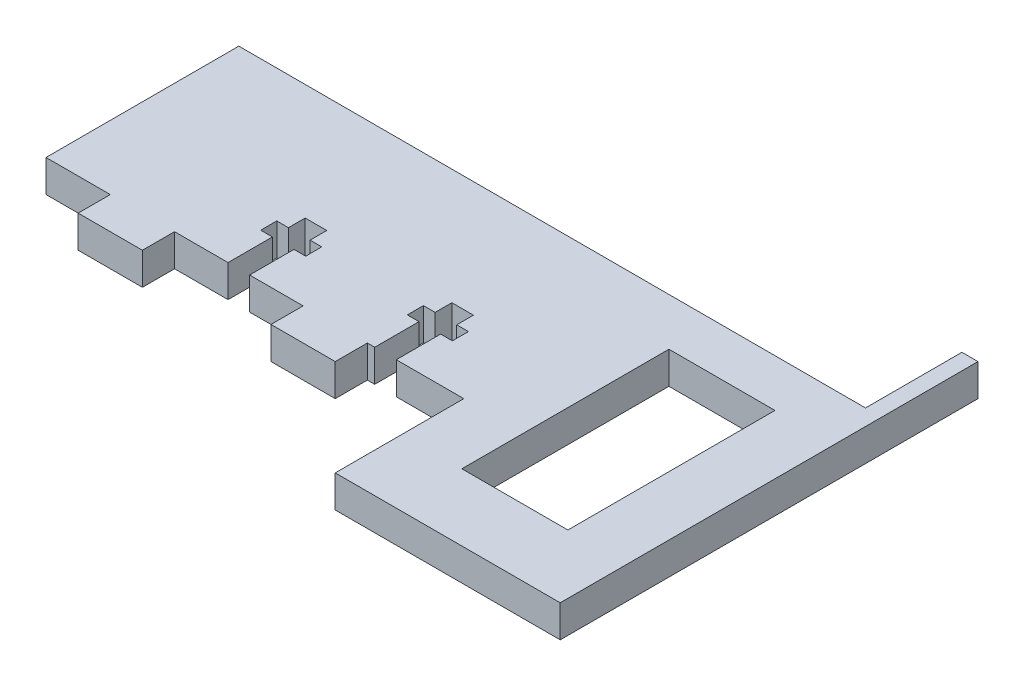
SolidWorks part; units mm, degrees
ref_plane "Front Plane" through (0, 0, 0) normal (0, 0, 1) x (1, 0, 0)
ref_plane "Top Plane" through (0, 0, 0) normal (0, 1, 0) x (1, 0, 0)
ref_plane "Right Plane" through (0, 0, 0) normal (1, 0, 0) x (0, 0, -1)
sketch "Sketch1" plane through (0, 0, 0) normal (0, 1, 0) x (1, 0, 0)
  line L0 (64.8104, 44.2474) -> (64.8104, -38.3026)
  line L1 (-62.1896, 44.2474) -> (64.8104, 44.2474)
  line L2 (-62.1896, 44.2474) -> (-62.1896, -12.9026)
  line L3 (-62.1896, -12.9026) -> (-49.4896, -12.9026)
  line L4 (-36.7896, -12.9026) -> (-11.3896, -12.9026)
  line L6 (1.3104, -12.9026) -> (1.3104, -19.2526)
  line L7 (64.8104, -38.3026) -> (20.3604, -38.3026)
  line L8 (20.3604, -12.9026) -> (20.3604, -38.3026)
  line L9 (1.3104, -19.2526) -> (-11.3896, -19.2526)
  line L10 (-11.3896, -12.9026) -> (-11.3896, -19.2526)
  line L11 (1.3104, -12.9026) -> (20.3604, -12.9026)
  line L12 (-36.7896, -12.9026) -> (-36.7896, -19.2526)
  line L13 (-36.7896, -19.2526) -> (-49.4896, -19.2526)
  line L14 (-49.4896, -12.9026) -> (-49.4896, -19.2526)
  dimension "D1" = 25.4
  dimension "D2" = 57.15
  dimension "D3" = 6.35
  dimension "D4" = 6.35
  dimension "D5" = 12.7
  dimension "D6" = 12.7
  dimension "D7" = 25.4
  dimension "D8" = 19.05
  dimension "D9" = 44.45
  dimension "D10" = 12.7
extrude "Boss-Extrude1" add sketch "Sketch1" along normal blind 6.35
sketch "Sketch2" plane through (0, 0, 0) normal (0, -1, 0) x (1, 0, 0)
  line L0 (20.3604, 12.9026) -> (23.5354, 40.7055)
  line L1 (61.6354, 40.7055) -> (61.6354, -44.2474)
  line L2 (64.8104, -44.2474) -> (-62.1896, -44.2474) construction
  line L3 (61.6354, -44.2474) -> (64.8104, -44.2474)
  line L4 (64.8104, -44.2474) -> (64.8104, 38.3026)
  line L5 (64.8104, 38.3026) -> (64.8104, -44.2474) construction
  line L6 (64.8104, 38.3026) -> (20.3604, 38.3026)
  line L7 (20.3604, 38.3026) -> (20.3604, 12.9026)
  arc A0 (61.6354, 40.7055) -> (23.5354, 40.7055) centre (42.5854, 40.7055) ccw
extrude "Cut-Extrude1" cut sketch "Sketch2" against normal through all rebuild error yes
sketch "Sketch4" plane through (0, 0, 0) normal (0, -1, 0) x (1, 0, 0)
  line L1 (32.1671, 25.0919) -> (53.1176, 25.0919)
  line L2 (32.1671, 25.0919) -> (32.1671, -15.8271)
  line L3 (32.1671, -15.8271) -> (53.1176, -15.8271)
  line L4 (53.1176, 25.0919) -> (53.1176, -15.8271)
extrude "Cut-Extrude2" cut sketch "Sketch4" against normal through all
sketch "Sketch5" plane through (0, 6.35, 0) normal (0, 1, 0) x (1, 0, 0)
  line L0 (-62.1896, 44.2474) -> (-62.1896, -12.9026) construction
  line L1 (61.6354, 44.2474) -> (-62.1896, 44.2474)
  line L2 (61.6354, 44.2474) -> (61.6354, 25.1974)
  line L3 (61.6354, 25.1974) -> (-62.1896, 25.1974)
  line L4 (-62.1896, 44.2474) -> (-62.1896, 25.1974)
  circle A0 centre (47.4162, -54.6607) radius 1.778
  circle A1 centre (37.417, -54.5392) radius 1.778
  circle A2 centre (48.0117, -5.6643) radius 1.778
  circle A3 centre (38.0124, -5.5428) radius 1.778
  dimension "D1" = 19.05
extrude "Cut-Extrude3" cut sketch "Sketch5" against normal through all
sketch "Sketch6" plane through (0, 6.35, 0) normal (0, 1, 0) x (1, 0, 0)
  line L1 (-36.7896, -12.9026) -> (-11.3896, -12.9026) construction
  line L2 (-24.0896, -12.9026) -> (-24.0896, 2.4668) construction
  line B0 (2.759, -12.9026) -> (7.0262, -12.9026)
  line B1 (7.0262, -0.9646) -> (9.3376, -0.9646)
  line B2 (9.3376, -0.9646) -> (9.3376, -4.1396)
  line B3 (9.3376, -4.1396) -> (7.0262, -4.1396)
  line B4 (7.0262, -4.1396) -> (7.0262, -12.9026)
  line B5 (7.0262, -0.9646) -> (7.0262, 2.3374)
  line B6 (7.0262, 2.3374) -> (2.759, 2.3374)
  line B7 (2.759, -0.9646) -> (2.759, 2.3374)
  line B8 (2.759, -4.1396) -> (2.759, -12.9026)
  line B9 (0.4476, -4.1396) -> (2.759, -4.1396)
  line B10 (0.4476, -0.9646) -> (0.4476, -4.1396)
  line B11 (2.759, -0.9646) -> (0.4476, -0.9646)
  line B12 (-26.2232, -12.9026) -> (-21.956, -12.9026)
  line B13 (-21.956, -0.9646) -> (-19.6446, -0.9646)
  line B14 (-19.6446, -0.9646) -> (-19.6446, -4.1396)
  line B15 (-19.6446, -4.1396) -> (-21.956, -4.1396)
  line B16 (-21.956, -4.1396) -> (-21.956, -12.9026)
  line B17 (-21.956, -0.9646) -> (-21.956, 2.3374)
  line B18 (-21.956, 2.3374) -> (-26.2232, 2.3374)
  line B19 (-26.2232, -0.9646) -> (-26.2232, 2.3374)
  line B20 (-26.2232, -4.1396) -> (-26.2232, -12.9026)
  line B21 (-28.5346, -4.1396) -> (-26.2232, -4.1396)
  line B22 (-28.5346, -0.9646) -> (-28.5346, -4.1396)
  line B23 (-26.2232, -0.9646) -> (-28.5346, -0.9646)
sketch_block_instance "TSlot-1"
sketch_block "TSlot" parameters "D1"=3.302, "D2"=3.175
sketch_block_instance "TSlot-3"
extrude "Cut-Extrude4" cut sketch "Sketch6" against normal through all
